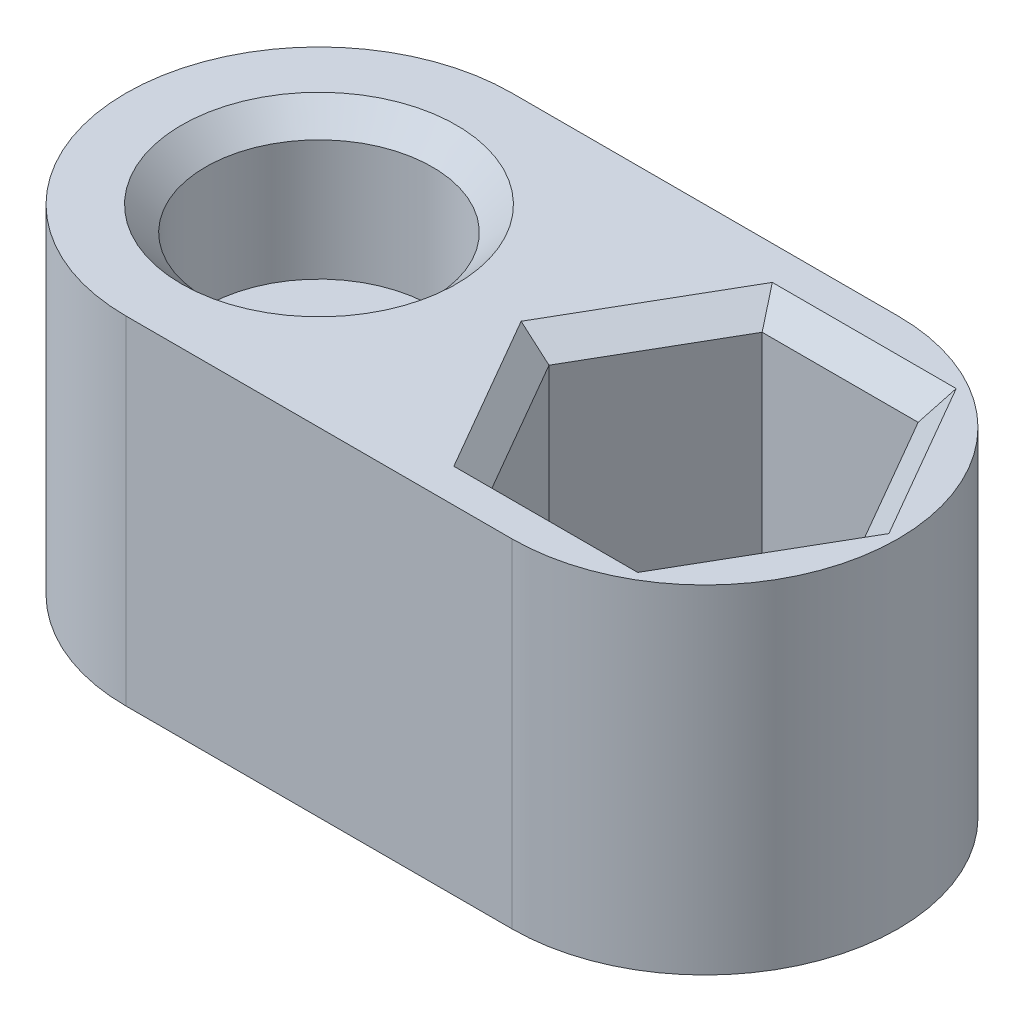
SolidWorks part; units mm, degrees
ref_plane "Front Plane" through (0, 0, 0) normal (0, 0, 1) x (1, 0, 0)
ref_plane "Top Plane" through (0, 0, 0) normal (0, 1, 0) x (1, 0, 0)
ref_plane "Right Plane" through (0, 0, 0) normal (1, 0, 0) x (0, 0, -1)
sketch "Sketch1" plane through (0, 0, 0) normal (0, 1, 0) x (1, 0, 0)
  line L0 (-4, 0) -> (4, 0) construction
  line L1 (-4, 4) -> (4, 4)
  line L2 (-4, -4) -> (4, -4)
  arc A0 (-4, 4) -> (-4, -4) centre (-4, 0) ccw
  arc A1 (4, -4) -> (4, 4) centre (4, 0) ccw
  point P2 (0, 0)
  dimension "D1" = 8
  dimension "D2" = 8
extrude "Boss-Extrude1" add sketch "Sketch1" along normal blind 7
sketch "Sketch2" plane through (0, 7, 0) normal (0, 1, 0) x (1, 0, 0)
  circle A0 centre (-4, 0) radius 2.35
  arc A1 (-4, 4) -> (-4, -4) centre (-4, 0) ccw construction
  dimension "D1" = 4.7
extrude "Cut-Extrude1" cut sketch "Sketch2" against normal blind 3
sketch "Sketch3" plane through (0, 0, 0) normal (0, -1, 0) x (1, 0, 0)
  circle A0 centre (-4, 0) radius 2.75
  arc A1 (-4, 4) -> (-4, -4) centre (-4, 0) ccw construction
  dimension "D1" = 5.5
extrude "Cut-Extrude2" cut sketch "Sketch3" against normal blind 2.5
sketch "Sketch4" plane through (0, 4, 0) normal (0, 1, 0) x (1, 0, 0)
  circle A0 centre (-4, 0) radius 1.3
  dimension "D1" = 2.6
extrude "Cut-Extrude3" cut sketch "Sketch4" against normal blind 1
sketch "Sketch5" plane through (0, 7, 0) normal (0, 1, 0) x (1, 0, 0)
  line L1 (7.2332, 0) -> (5.6166, 2.8)
  line L2 (5.6166, 2.8) -> (2.3834, 2.8)
  line L3 (2.3834, 2.8) -> (0.7668, 0)
  line L4 (0.7668, 0) -> (2.3834, -2.8)
  line L5 (2.3834, -2.8) -> (5.6166, -2.8)
  line L6 (5.6166, -2.8) -> (7.2332, 0)
  circle A0 centre (4, 0) radius 2.8 construction
  arc A1 (4, -4) -> (4, 4) centre (4, 0) ccw construction
  dimension "D1" = 5.6
extrude "Cut-Extrude4" cut sketch "Sketch5" against normal blind 6
sketch "Sketch6" plane through (0, 1, 0) normal (0, 1, 0) x (1, 0, 0)
  circle A0 centre (4, 0) radius 1.6
  arc A1 (4, -4) -> (4, 4) centre (4, 0) ccw construction
  dimension "D1" = 3.2
extrude "Cut-Extrude5" cut sketch "Sketch6" against normal through all
chamfer "Chamfer1" distance 0.5 angle 45 7 edges at (-4, 7, 2.35) (6.4249, 7, -1.4) (6.4249, 7, 1.4) (4, 7, 2.8) (1.5751, 7, 1.4) (1.5751, 7, -1.4) (4, 7, -2.8)
